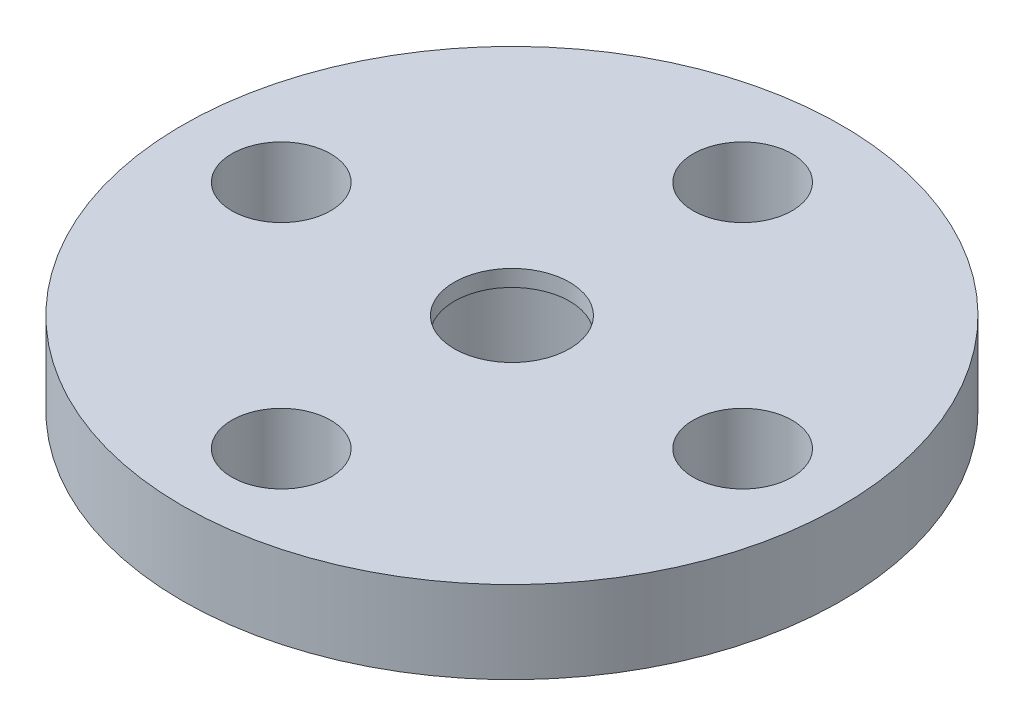
SolidWorks part; units mm, degrees
ref_plane "Front Plane" through (0, 0, 0) normal (0, 0, 1) x (1, 0, 0)
ref_plane "Top Plane" through (0, 0, 0) normal (0, 1, 0) x (1, 0, 0)
ref_plane "Right Plane" through (0, 0, 0) normal (1, 0, 0) x (0, 0, -1)
sketch "Sketch1" plane through (0, 0, 0) normal (0, 1, 0) x (1, 0, 0)
  circle A0 centre (0, 0) radius 10
extrude "Boss-Extrude1" add sketch "Sketch1" along normal blind 2.5
sketch "Sketch2" plane through (0, 0, 0) normal (0, -1, 0) x (1, 0, 0)
  circle A0 centre (0, 0) radius 3
  circle A1 centre (0, 0) radius 4.5
extrude "Boss-Extrude2" add sketch "Sketch2" along normal blind 2
sketch "Sketch3" plane through (0, 2.5, 0) normal (0, 1, 0) x (1, 0, 0)
  circle A0 centre (0, 0) radius 7 construction
  circle A1 centre (0, 7) radius 1.5
  circle A2 centre (7, 0) radius 1.5
  circle A3 centre (0, -7) radius 1.5
  circle A4 centre (-7, 0) radius 1.5
  circle A5 centre (0, 0) radius 1.75
  dimension "D1" = 4
extrude "Cut-Extrude1" cut sketch "Sketch3" against normal through all
extrude "Cut-Extrude2" cut sketch "Sketch2<2>" against normal blind 2 contours A0 region at (0, 0, 0)
sketch "Sketch2<2>" plane through (0, 0, 0) normal (0, -1, 0) x (1, 0, 0) same geometry as "Sketch2"
